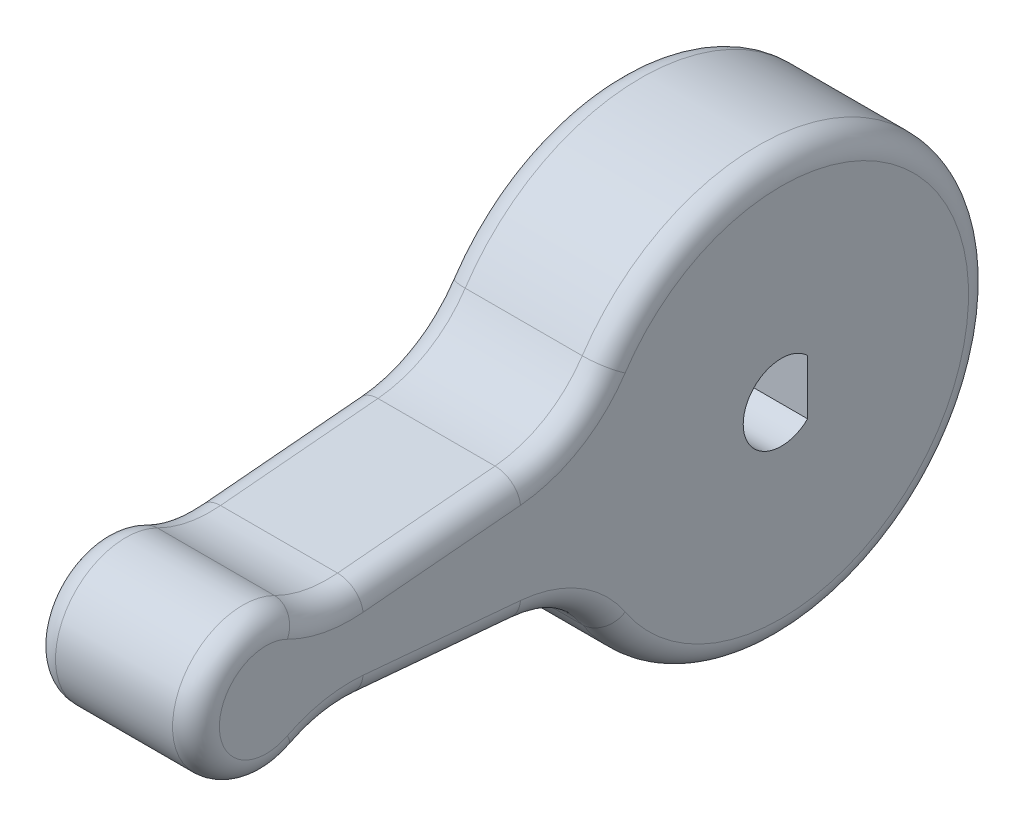
SolidWorks part; units mm, degrees
material "ABS"
ref_plane "Front Plane" through (0, 0, 0) normal (0, 0, 1) x (1, 0, 0)
ref_plane "Top Plane" through (0, 0, 0) normal (0, 1, 0) x (1, 0, 0)
ref_plane "Right Plane" through (0, 0, 0) normal (1, 0, 0) x (0, 0, -1)
sketch "Sketch1" plane through (0, 0, 0) normal (1, 0, 0) x (0, 0, -1)
  line L0 (1.125, -1.1726) -> (1.125, 1.1726)
  line L1 (-25, 0) -> (-22, 0) construction
  line L2 (-22, 0) -> (0, 0) construction
  line L3 (-19.7639, 2) -> (-8.4853, 3)
  line L4 (-19.7639, -2) -> (-8.4853, -3)
  line L5 (0, 0) -> (9, 0) construction
  line L6 (-1.625, 0) -> (1.125, 0) construction
  arc A0 (1.125, 1.1726) -> (1.125, -1.1726) centre (0, 0) ccw
  arc A1 (-8.4853, -3) -> (-8.4853, 3) centre (0, 0) ccw
  arc A2 (-19.7639, 2) -> (-19.7639, -2) centre (-22, 0) ccw
  dimension "D1" = 6
  dimension "D2" = 18
  dimension "D4" = 6
  dimension "D6" = 1.625
  dimension "D3" = 25
  dimension "D5" = 4
  dimension "D7" = 2.75
extrude "Boss-Extrude1" add sketch "Sketch1" along normal mid plane 7
fillet "Fillet1" radius 5 4 edges at (0, 2, 19.7639) (0, -3, 8.4853) (0, -2, 19.7639) (0, 3, 8.4853)
ref_plane "Plane1" through (0, 0, -9.125) normal (0, 0, 1) x (1, 0, 0)
hole_wizard "Hole1" positions "Sketch2" profile "Sketch3" legacy
sketch "Sketch2" plane through (0, 0, -9.125) normal (0, 0, 1) x (1, 0, 0)
  point P0 (0, 0)
  point P4 (0, 0)
sketch "Sketch3" plane through (0, 0, -9.125) normal (1, 0, 0) x (0, 1, 0)
  line L0 (0, 0) -> (0, 9)
  line L1 (0, 9) -> (1.5, 9)
  line L2 (1.5, 9) -> (1.5, 4)
  line L3 (1.5, 4) -> (2, 4)
  line L4 (2, 4) -> (2, 0)
  line L5 (2, 0) -> (0, 0)
  line L6 (0, 110) -> (0, -10) construction
  dimension "Diameter" = 3
  dimension "Depth" = 9
  dimension "C-Bore Diameter" = 4
  dimension "C-Bore Depth" = 4
fillet "Fillet2" radius 1 16 edges at (-3.5, -3.4408, 9.1105) (-3.5, -2.4588, 14.5891) (-3.5, -2.2307, 19.3361) (-3.5, 0, 25) (-3.5, 2.2307, 19.3361) (-3.5, 2.4588, 14.5891) (-3.5, 3.4408, 9.1105) (3.5, -3.4408, 9.1105) (3.5, -2.4588, 14.5891) (3.5, -2.2307, 19.3361) (3.5, 0, 25) (3.5, 2.2307, 19.3361) (3.5, 2.4588, 14.5891) (3.5, 3.4408, 9.1105) (-3.5, 0, -9) (3.5, 0, -9)
